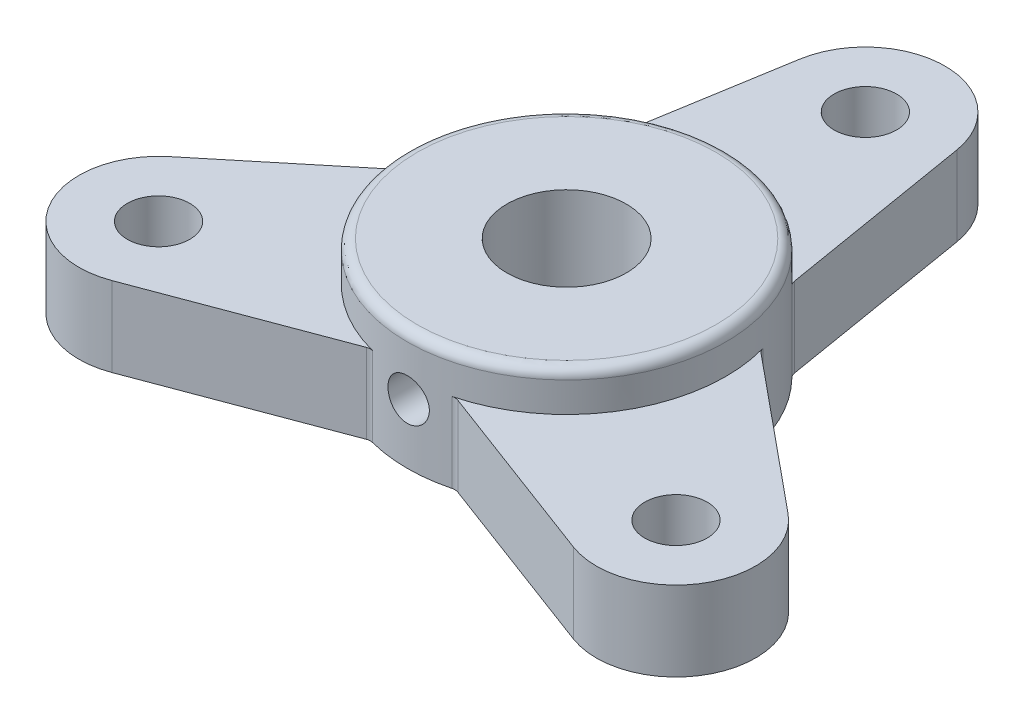
SolidWorks part; units mm, degrees
material "ABS"
ref_plane "Front Plane" through (0, 0, 0) normal (0, 0, 1) x (1, 0, 0)
ref_plane "Top Plane" through (0, 0, 0) normal (0, 1, 0) x (1, 0, 0)
ref_plane "Right Plane" through (0, 0, 0) normal (1, 0, 0) x (0, 0, -1)
sketch "Sketch1" plane through (0, 0, 0) normal (0, 1, 0) x (1, 0, 0)
  line L0 (-6.2639, 24.8546) -> (-8.89, 9.0696)
  line L1 (6.2639, 24.8546) -> (8.89, 9.0696)
  line L2 (18.3928, -17.852) -> (3.4095, -12.2338)
  line L3 (24.6567, -7.0026) -> (12.2995, 3.1642)
  line L4 (-24.6567, -7.0026) -> (-12.2995, 3.1642)
  line L5 (-18.3928, -17.852) -> (-3.4095, -12.2338)
  circle A0 centre (0, 0) radius 30.1625 construction
  circle A1 centre (0, 0) radius 23.8125 construction
  circle A2 centre (0, 23.8125) radius 2.4892 construction
  circle A3 centre (0, 0) radius 12.7
  circle A4 centre (0, 0) radius 4.7625
  circle A5 centre (20.6222, 11.9063) radius 2.4892 construction
  circle A6 centre (20.6222, -11.9062) radius 2.4892 construction
  circle A7 centre (0, -23.8125) radius 2.4892 construction
  circle A8 centre (-20.6222, -11.9063) radius 2.4892 construction
  circle A9 centre (-20.6222, 11.9062) radius 2.4892 construction
  arc A10 (-6.2639, 24.8546) -> (6.2639, 24.8546) centre (0, 23.8125) cw
  arc A11 (24.6567, -7.0026) -> (18.3928, -17.852) centre (20.6222, -11.9063) cw
  arc A12 (-18.3928, -17.852) -> (-24.6567, -7.0026) centre (-20.6222, -11.9063) cw
  point P20 (0, 0)
  point P23 (0, 0)
  point P24 (7.6892, 10.1077)
  point P35 (0, 0)
  point P36 (14.6723, 4.6303)
  point P37 (0, 0)
  point P38 (0, 0)
  dimension "D1" = 4.9784
  dimension "D2" = 47.625
  dimension "D3" = 60.325
  dimension "D4" = 9.525
  dimension "D5" = 25.4
  dimension "D8" = 17.78
  dimension "D6" = 6
  dimension "D7" = 3
extrude "Boss-Extrude1" add sketch "Sketch1" against normal blind 6.35 contours A10 L0 A3 L1 | A3 A4 | A11 L3 A3 L2 | A12 L5 A3 L4 region at (0, 0, -19.7537) region at (0, 0, -12.3408) region at (-17.1072, 0, 9.8768) region at (17.1072, 0, 9.8768)
extrude "Boss-Extrude2" add sketch "Sketch1<5>" along normal blind 3.175 contours A3 A4 region at (0, 0, -12.3408)
sketch "Sketch1<5>" plane through (0, 0, 0) normal (0, 1, 0) x (1, 0, 0) same geometry as "Sketch1"
hole_wizard "#10 Clearance Hole1" positions "3DSketch1" profile "Sketch2" hole size "#10" standard "ANSI Inch" end condition through all
sketch3d "3DSketch1"
  point P0 (0, 0, -23.8125)
  point P2 (20.6222, 0, 11.9062)
  point P4 (-20.6222, 0, 11.9063)
  point P7 (-20.6222, 0, 11.9063)
  point P9 (0, 0, -23.8125)
  point P11 (20.6222, 0, 11.9062)
sketch "Sketch2" plane through (0, 0, -23.8125) normal (1, 0, 0) x (0, 0, 1)
  line L0 (0, 0) -> (0, 6.35)
  line L1 (0, 6.35) -> (2.4892, 6.35)
  line L2 (2.4892, 6.35) -> (2.4892, 0)
  line L5 (2.4892, 0) -> (0, 0)
  line L11 (0, -6.35) -> (0, 107.95) construction
  dimension "Thru Hole Dia." = 4.9784
  dimension "Thru Hole Depth" = 6.35
ref_plane "Plane1" through (0, 0, 12.7) normal (0, 0, 1) x (1, 0, 0)
sketch "Sketch4" plane through (0, 0, 12.7) normal (0, 0, 1) x (1, 0, 0)
  line L0 (0, 3.175) -> (0, -6.35)
  line L1 (12.7, 3.175) -> (-12.7, 3.175) construction
  line L2 (-3.4095, -6.35) -> (3.4095, -6.35) construction
  circle A0 centre (0, -1.5875) radius 2
  dimension "D1" = 4
hole_wizard "Tap Drill for M4x0.7 Tap1" positions "3DSketch2" profile "Sketch5" hole size "M4x0.7" standard "ANSI Metric" end condition up to next
sketch3d "3DSketch2"
  point P0 (0, -1.5875, 12.7)
  point P3 (0, -1.5875, 12.7)
sketch "Sketch5" plane through (0, -1.5875, 12.7) normal (1, 0, 0) x (0, -1, 0)
  line L0 (0, 0) -> (0, 7.9375)
  line L1 (0, 7.9375) -> (1.65, 7.9375)
  line L2 (1.65, 7.9375) -> (1.65, 0)
  line L5 (1.65, 0) -> (0, 0)
  line L11 (0, -6.35) -> (0, 107.95) construction
  dimension "Thru Hole Dia." = 3.3
  dimension "Thru Hole Depth" = 7.9375
fillet "Fillet1" radius 0.7937 7 edges at (12.2995, -3.175, -3.1642) (-12.2995, -3.175, -3.1642) (-8.89, -3.175, -9.0696) (8.89, -3.175, -9.0696) (3.4095, -3.175, 12.2338) (-3.4095, -3.175, 12.2338) (0, 3.175, 12.7)
